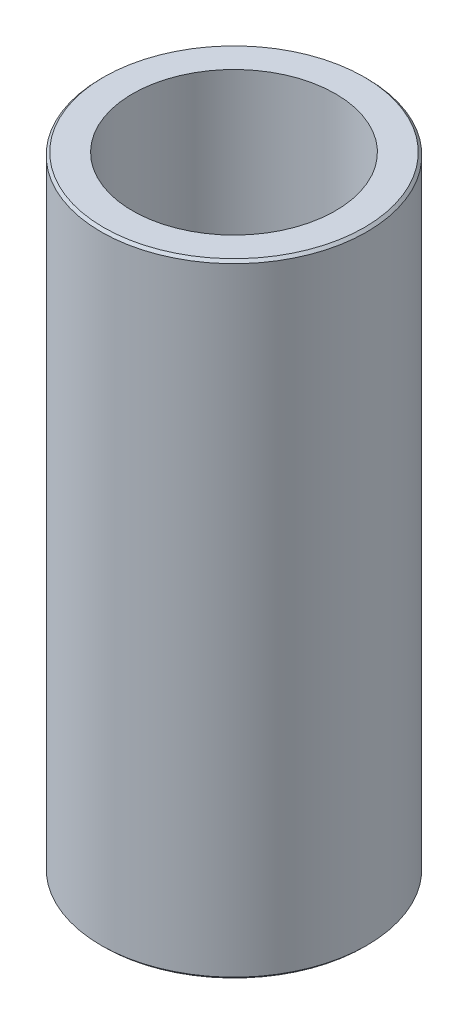
SolidWorks part; units mm, degrees
ref_plane "Front Plane" through (0, 0, 0) normal (0, 0, 1) x (1, 0, 0)
ref_plane "Top Plane" through (0, 0, 0) normal (0, 1, 0) x (1, 0, 0)
ref_plane "Right Plane" through (0, 0, 0) normal (1, 0, 0) x (0, 0, -1)
sketch "Sketch1" plane through (0, 0, 0) normal (0, 1, 0) x (1, 0, 0)
  circle A0 centre (0, 0) radius 25
  dimension "SHAFT_OD" = 50
extrude "Boss-Extrude1" add sketch "Sketch1" along normal blind 117.2305
sketch "Sketch2" plane through (0, 0, 0) normal (0, 1, 0) x (1, 0, 0)
  circle A0 centre (0, 0) radius 19.0898
  dimension "BORE_D" = 38.1796
extrude "Cut-Extrude1" cut sketch "Sketch2" along normal through all
chamfer "Chamfer1" distance 0.4784 angle 45 2 edges at (0, 117.2305, 25) (0, 0, 25)
